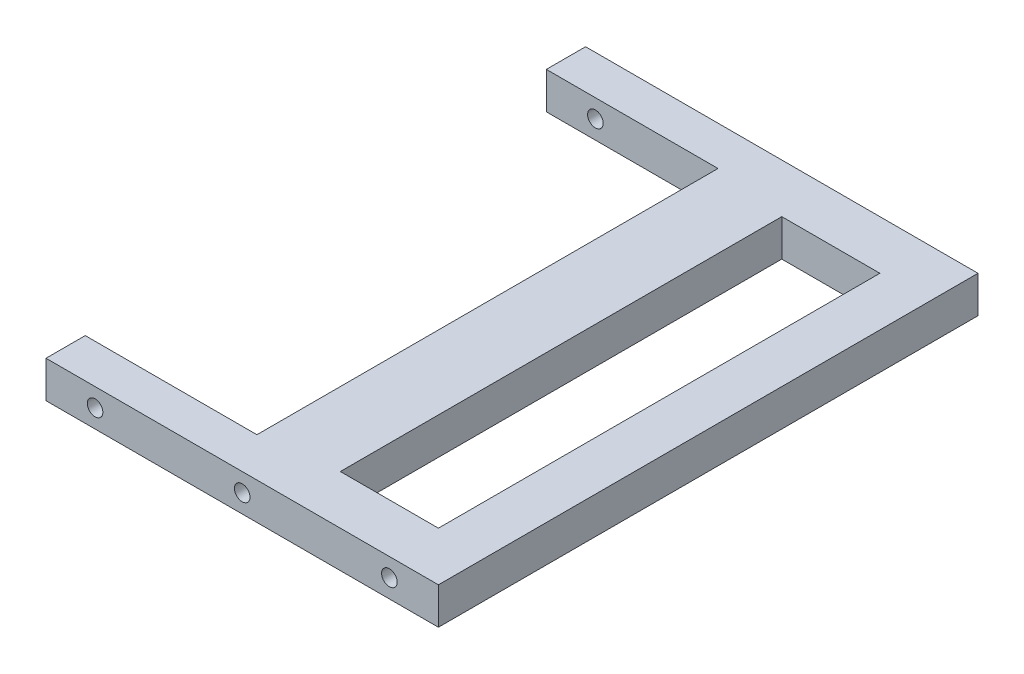
SolidWorks part; units mm, degrees
material "ABS"
ref_plane "Front Plane" through (0, 0, 0) normal (0, 0, 1) x (1, 0, 0)
ref_plane "Top Plane" through (0, 0, 0) normal (0, 1, 0) x (1, 0, 0)
ref_plane "Right Plane" through (0, 0, 0) normal (1, 0, 0) x (0, 0, -1)
sketch "Sketch1" plane through (0, 0, 0) normal (0, 1, 0) x (1, 0, 0)
  line L1 (-50.8, -69.85) -> (50.8, -69.85)
  line L2 (-50.8, -69.85) -> (-50.8, 69.85)
  line L3 (-50.8, 69.85) -> (50.8, 69.85)
  line L4 (50.8, -69.85) -> (50.8, 69.85)
  line L5 (-50.8, -69.85) -> (50.8, 69.85) construction
  line L6 (-50.8, 69.85) -> (50.8, -69.85) construction
  point P0 (0, 0)
  dimension "D1" = 139.7
  dimension "D2" = 101.6
extrude "Boss-Extrude1" add sketch "Sketch1" along normal blind 9.525
sketch "Sketch2" plane through (0, 9.525, 0) normal (0, 1, 0) x (1, 0, 0)
  line L0 (-50.8, 69.85) -> (-50.8, -69.85) construction
  line L1 (38.1, 57.15) -> (12.7, 57.15)
  line L2 (38.1, 57.15) -> (38.1, -57.15)
  line L3 (38.1, -57.15) -> (12.7, -57.15)
  line L4 (12.7, 57.15) -> (12.7, -57.15)
  line L5 (-50.8, 59.69) -> (-6.35, 59.69)
  line L6 (-50.8, 59.69) -> (-50.8, -59.69)
  line L7 (-50.8, -59.69) -> (-6.35, -59.69)
  line L8 (-6.35, 59.69) -> (-6.35, -59.69)
extrude "Cut-Extrude1" cut sketch "Sketch2" against normal blind 9.525
hole_wizard "#10-32 Tapped Hole1" positions "3DSketch1" profile "Sketch3" tap size "#10-32" standard "Ansi Inch"
sketch3d "3DSketch1"
  line L0 (-50.8, 4.7625, 69.85) -> (50.8, 4.7625, 69.85) construction
  line L1 (-50.8, 9.525, 69.85) -> (-50.8, 0, 69.85) construction
  line L2 (50.8, 9.525, 69.85) -> (50.8, 0, 69.85) construction
  line L4 (-50.8, 9.525, 69.85) -> (50.8, 9.525, 69.85) construction
  line L5 (-38.1, 9.525, 69.85) -> (-38.1, 0, 69.85) construction
  line L6 (-50.8, 0, 69.85) -> (50.8, 0, 69.85) construction
  line L7 (38.1, 9.525, 69.85) -> (38.1, 0, 69.85) construction
  line L9 (0, 9.525, 69.85) -> (0, 0, 69.85) construction
  line L10 (50.8, 4.7625, -69.85) -> (-50.8, 4.7625, -69.85) construction
  line L11 (50.8, 9.525, -69.85) -> (50.8, 0, -69.85) construction
  line L12 (-50.8, 9.525, -69.85) -> (-50.8, 0, -69.85) construction
  line L13 (38.1, 9.525, -69.85) -> (38.1, 0, -69.85) construction
  line L14 (50.8, 9.525, -69.85) -> (-50.8, 9.525, -69.85) construction
  line L15 (50.8, 0, -69.85) -> (-50.8, 0, -69.85) construction
  line L16 (0, 0, -69.85) -> (0, 9.525, -69.85) construction
  line L17 (-38.1, 0, -69.85) -> (-38.1, 9.525, -69.85) construction
  point P0 (-38.1, 4.7625, 69.85)
  point P2 (0, 4.7625, 69.85)
  point P4 (38.1, 4.7625, 69.85)
  point P8 (38.1, 4.7625, -69.85)
  point P10 (0, 4.7625, -69.85)
  point P12 (-38.1, 4.7625, -69.85)
  dimension "D1" = 12.7
  dimension "D2" = 12.7
  dimension "D3" = 12.7
  dimension "D4" = 12.7
sketch "Sketch3" plane through (-38.1, 4.7625, 69.85) normal (1, 0, 0) x (0, -1, 0)
  line L0 (0, 0) -> (0, 14.9293)
  line L1 (0, 14.9293) -> (2.0193, 13.716)
  line L2 (2.0193, 13.716) -> (2.0193, 0)
  line L5 (2.0193, 0) -> (0, 0)
  line L10 (0, 14.9293) -> (-2.0193, 13.716) construction
  line L11 (0, -6.35) -> (0, 107.95) construction
  dimension "Tap Drill Dia." = 4.0386
  dimension "Tap Drill Depth" = 13.716
  dimension "Drill Angle" = 118
cosmetic thread "Hole Thread1" parameters "D1"=9.652, "D2"=4.826
cosmetic thread "Hole Thread2" parameters "D1"=9.652, "D2"=4.826
cosmetic thread "Hole Thread3" parameters "D1"=9.652, "D2"=4.826
cosmetic thread "Hole Thread4" parameters "D1"=9.652, "D2"=4.826
cosmetic thread "Hole Thread5" parameters "D1"=9.652, "D2"=4.826
cosmetic thread "Hole Thread6" parameters "D1"=9.652, "D2"=4.826
